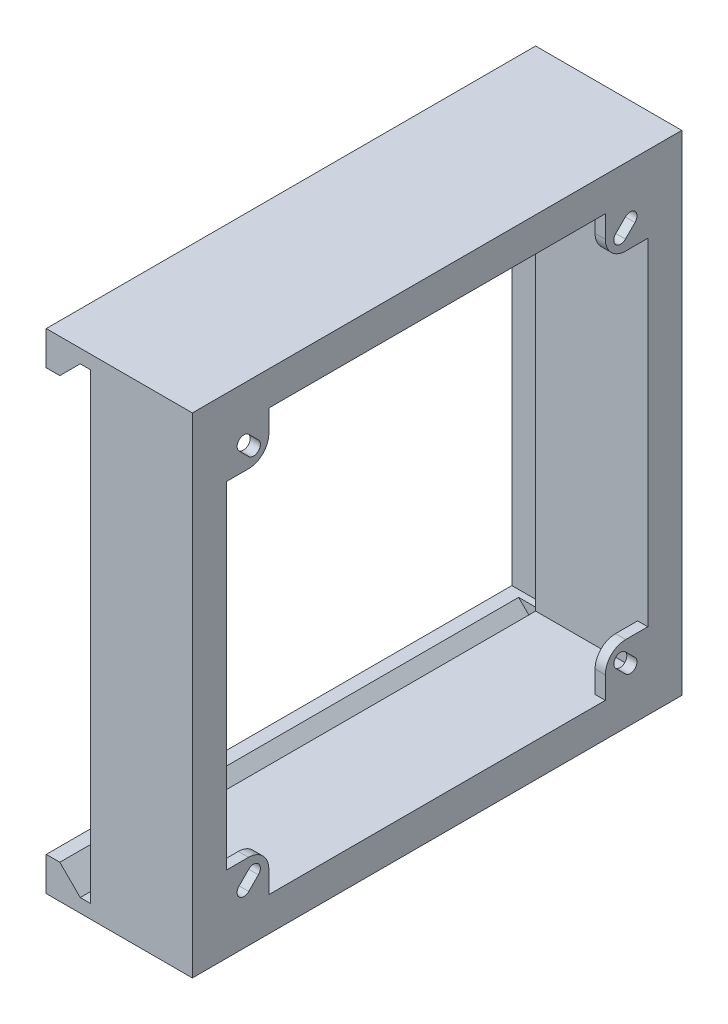
SolidWorks part; units mm, degrees
ref_plane "Front Plane" through (0, 0, 0) normal (1, 0, 0) x (0, 1, 0)
ref_plane "Top Plane" through (0, 0, 0) normal (0, 0, 1) x (0, 1, 0)
ref_plane "Right Plane" through (0, 0, 0) normal (0, 1, 0) x (-1, 0, 0)
sketch "Sketch2" plane through (0, 0, 0) normal (1, 0, 0) x (0, 1, 0)
  line L0 (-72, -72) -> (-72, 72)
  line L1 (-62, -62) -> (62, -62)
  line L2 (-62, -62) -> (-62, 62)
  line L3 (-62, 62) -> (62, 62)
  line L4 (62, -62) -> (62, 62)
  line L5 (-62, -62) -> (62, 62) construction
  line L6 (-62, 62) -> (62, -62) construction
  line L7 (-72, 72) -> (72, 72)
  line L8 (72, -72) -> (72, 72)
  line L9 (-72, -72) -> (72, -72)
  line L10 (-49.5, 62) -> (-49.5, 55.5)
  line L11 (-55.5, 49.5) -> (-62, 49.5)
  line L12 (-54, 54) -> (-56.8284, 56.8284) construction
  line L13 (-55.4142, 52.5858) -> (-58.2426, 55.4142)
  line L14 (-52.5858, 55.4142) -> (-55.4142, 58.2426)
  line L15 (49.5, 55.5) -> (49.5, 62)
  line L16 (62, 49.5) -> (55.5, 49.5)
  line L17 (54, 54) -> (56.8284, 56.8284) construction
  line L18 (52.5858, 55.4142) -> (55.4142, 58.2426)
  line L19 (55.4142, 52.5858) -> (58.2426, 55.4142)
  line L20 (55.5, -49.5) -> (62, -49.5)
  line L21 (49.5, -62) -> (49.5, -55.5)
  line L22 (54, -54) -> (56.8284, -56.8284) construction
  line L23 (55.4142, -52.5858) -> (58.2426, -55.4142)
  line L24 (52.5858, -55.4142) -> (55.4142, -58.2426)
  line L25 (-49.5, -55.5) -> (-49.5, -62)
  line L26 (-62, -49.5) -> (-55.5, -49.5)
  line L27 (-54, -54) -> (-56.8284, -56.8284) construction
  line L28 (-52.5858, -55.4142) -> (-55.4142, -58.2426)
  line L29 (-55.4142, -52.5858) -> (-58.2426, -55.4142)
  arc A0 (-49.5, 55.5) -> (-55.5, 49.5) centre (-55.5, 55.5) cw
  arc A2 (-55.4142, 52.5858) -> (-52.5858, 55.4142) centre (-54, 54) ccw
  arc A3 (-55.4142, 58.2426) -> (-58.2426, 55.4142) centre (-56.8284, 56.8284) ccw
  arc A4 (55.5, 49.5) -> (49.5, 55.5) centre (55.5, 55.5) cw
  arc A5 (52.5858, 55.4142) -> (55.4142, 52.5858) centre (54, 54) ccw
  arc A6 (58.2426, 55.4142) -> (55.4142, 58.2426) centre (56.8284, 56.8284) ccw
  arc A7 (49.5, -55.5) -> (55.5, -49.5) centre (55.5, -55.5) cw
  arc A8 (55.4142, -52.5858) -> (52.5858, -55.4142) centre (54, -54) ccw
  arc A9 (55.4142, -58.2426) -> (58.2426, -55.4142) centre (56.8284, -56.8284) ccw
  arc A10 (-55.5, -49.5) -> (-49.5, -55.5) centre (-55.5, -55.5) cw
  arc A11 (-52.5858, -55.4142) -> (-55.4142, -52.5858) centre (-54, -54) ccw
  arc A12 (-58.2426, -55.4142) -> (-55.4142, -58.2426) centre (-56.8284, -56.8284) ccw
  point P0 (0, 0)
  point P14 (-51.2574, 51.2574)
  point P18 (-55.4142, 55.4142)
  point P33 (55.4142, 55.4142)
  point P45 (55.4142, -55.4142)
  point P57 (-55.4142, -55.4142)
  point P62 (0, 0)
  dimension "D4" = 6
  dimension "D6" = 2
  dimension "D8" = 4
  dimension "D1" = 124
  dimension "D2" = 124
  dimension "D5" = 12.5
  dimension "D7" = 8
  dimension "D3" = 10
  dimension "D9" = 4
extrude "Boss-Extrude1" add sketch "Sketch2" along normal blind 3 contours A0 L10 L3 L2 L11 A3 L14 A2 L13 | L0 L9 L8 L7 L4 L1 L2 L3 | A4 L16 L4 L3 L15 A6 L19 A5 L18 | A7 L21 L1 L4 L20 A9 L24 A8 L23 | A10 L26 L2 L1 L25 A12 L29 A11 L28 region at (0, -69.9635, 0) region at (0, -61.8232, -55.75) region at (0, 49.6768, -58.75) region at (0, -61.8232, 55.75) region at (0, 58.75, 49.6768)
extrude "Boss-Extrude2" add sketch "Sketch2<4>" against normal blind 30 contours L0 L9 L8 L7 L4 L1 L2 L3 region at (0, -69.9635, 0)
sketch "Sketch2<4>" plane through (0, 0, 0) normal (1, 0, 0) x (0, 1, 0) same geometry as "Sketch2"
sketch "Sketch3" plane through (-30, 0, 0) normal (-1, 0, 0) x (0, -1, 0)
  line L0 (-62, -62) -> (-62, 62)
  line L1 (-62, 62) -> (-62, 72)
  line L2 (72, 72) -> (-72, 72) construction
  line L3 (-62, 72) -> (-72, 72)
  line L4 (72, -72) -> (72, 72)
  line L5 (72, 72) -> (-72, 72)
  line L6 (-72, 72) -> (-72, -72)
  line L7 (-72, -72) -> (72, -72)
  line L8 (72, -72) -> (72, 72)
  line L10 (-72, 72) -> (-72, -72)
  line L11 (-72, -72) -> (72, -72)
  line L12 (72, 72) -> (62, 72)
  line L13 (62, 72) -> (62, 62)
  line L14 (62, 62) -> (62, -62)
  line L15 (62, -62) -> (-62, -62)
  dimension "D1" = 0
extrude "Boss-Extrude3" add sketch "Sketch3" along normal blind 10
sketch "Sketch6" plane through (0, 0, -62) normal (0, 0, 1) x (1, 0, 0)
  line L0 (-30, 62) -> (-30, 68)
  line L1 (-30, 68) -> (-36, 62)
  line L2 (-36, 62) -> (-30, 62)
  line L6 (-40, 62) -> (0, 62) construction
  line L7 (-30, -62) -> (-30, 62) construction
  line L8 (24.75, 0) -> (-24.75, 0) construction
  line L9 (-30, -68) -> (-36, -62)
  line L10 (-30, -62) -> (-30, -68)
  line L11 (-36, -62) -> (-30, -62)
  dimension "D1" = 45
  dimension "D2" = 6
extrude "Cut-Extrude3" cut sketch "Sketch6" along normal up to surface (134 mm away) from offset 1 up to face at (-26.75, 0, 72) offset against normal yes
sketch "Sketch5" plane through (-40, 0, 0) normal (-1, 0, 0) x (0, -1, 0)
  line L0 (-62, -62) -> (62, -62)
  line L1 (62, -62) -> (62, -65)
  line L2 (62, -65) -> (-62, -65)
  line L3 (-62, -65) -> (-62, -62)
  dimension "D1" = 3
extrude "Cut-Extrude2" cut sketch "Sketch5" against normal up to surface (10 mm away) up to face at (-30, 0, -10.8)
sketch "Sketch9" plane through (0, -72, 0) normal (0, -1, 0) x (1, 0, 0)
  line L1 (3, 72) -> (-40, 72) construction
  line L3 (-30, 69) -> (-27, 72)
  line L4 (-30, 72) -> (-30, -63) construction
  line L5 (-27, 72) -> (-30, 72)
  line L6 (-30, 72) -> (-30, 69)
  dimension "D1" = 45
  dimension "D2" = 3
extrude "Cut-Extrude4" cut sketch "Sketch9" against normal up to vertex (140 mm away) and the other way up to vertex (-4 mm away) from surface up to point (-30, 68, 72) other way up to point (-30, -68, 72) starting at plane "Right Plane"
